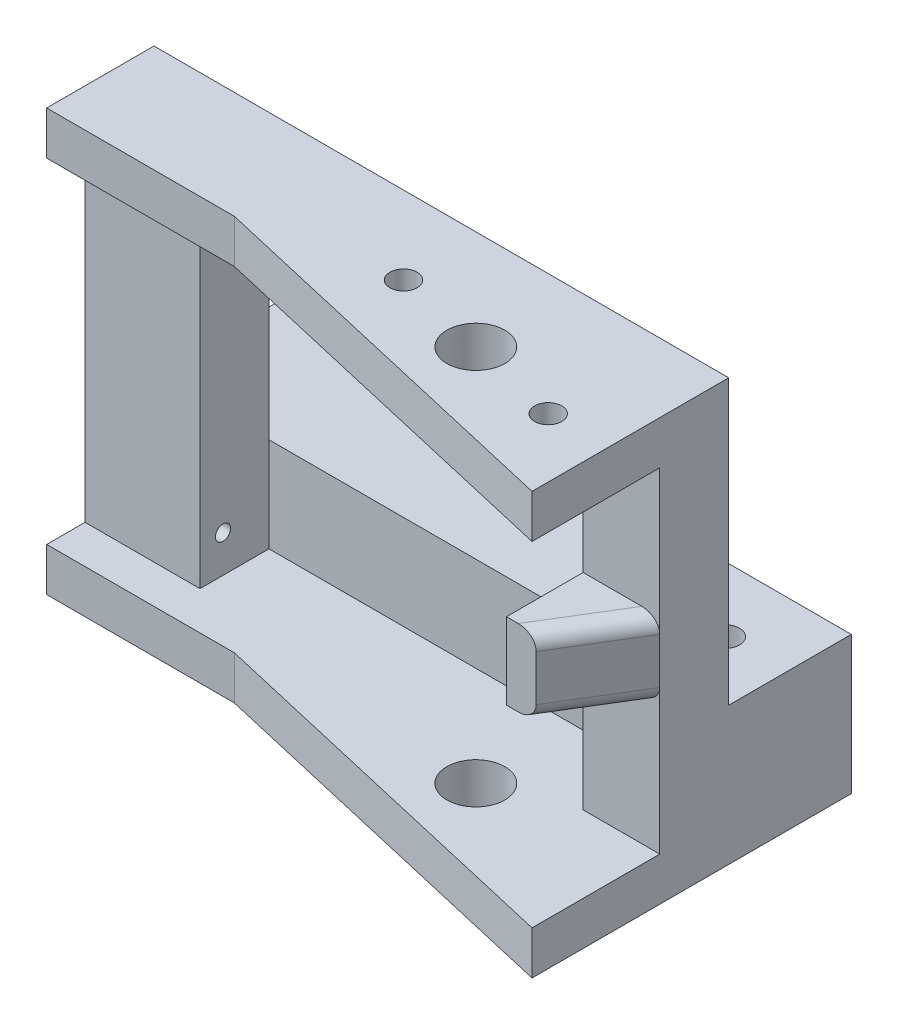
SolidWorks part; units mm, degrees
ref_plane "Front Plane" through (0, 0, 0) normal (0, 0, 1) x (1, 0, 0)
ref_plane "Top Plane" through (0, 0, 0) normal (0, 1, 0) x (1, 0, 0)
ref_plane "Right Plane" through (0, 0, 0) normal (1, 0, 0) x (0, 0, -1)
sketch "Sketch1" plane through (0, 0, 0) normal (0, 0, 1) x (1, 0, 0)
  line L1 (57.15, -34.925) -> (-57.15, -34.925)
  line L2 (57.15, -34.925) -> (57.15, 34.925)
  line L3 (57.15, 34.925) -> (-57.15, 34.925)
  line L4 (-57.15, -34.925) -> (-57.15, 34.925)
  line L5 (57.15, -34.925) -> (-57.15, 34.925) construction
  line L6 (57.15, 34.925) -> (-57.15, -34.925) construction
  point P0 (0, 0)
  dimension "D1" = 69.85
  dimension "D2" = 114.3
extrude "Boss-Extrude1" add sketch "Sketch1" along normal blind 57.15
sketch "Sketch2" plane through (0, 0, 57.15) normal (0, 0, 1) x (1, 0, 0)
  line L0 (-57.15, 34.925) -> (-57.15, -34.925) construction
  line L1 (57.15, -27.725) -> (-57.15, -27.725)
  line L2 (57.15, -27.725) -> (57.15, 27.725)
  line L3 (57.15, 27.725) -> (-57.15, 27.725)
  line L4 (-57.15, -27.725) -> (-57.15, 27.725)
  line L5 (57.15, -27.725) -> (-57.15, 27.725) construction
  line L6 (57.15, 27.725) -> (-57.15, -27.725) construction
  line L7 (57.15, 34.925) -> (-57.15, 34.925) construction
  point P0 (0, 0)
  dimension "D1" = 7.2
extrude "Cut-Extrude2" cut sketch "Sketch2" against normal blind 25.4
sketch "Sketch3" plane through (0, 0, 0) normal (0, 0, -1) x (-1, 0, 0)
  line L0 (-57.15, -34.925) -> (-57.15, 34.925) construction
  line L1 (57.15, 34.925) -> (-57.15, 34.925)
  line L2 (57.15, 34.925) -> (57.15, -12.065)
  line L3 (57.15, -12.065) -> (-57.15, -12.065)
  line L4 (-57.15, 34.925) -> (-57.15, -12.065)
  dimension "D1" = 46.99
extrude "Cut-Extrude3" cut sketch "Sketch3" against normal blind 20.32
sketch "Sketch5" plane through (0, -34.925, 0) normal (0, -1, 0) x (1, 0, 0)
  line L0 (-3.81, 10.79) -> (46.99, 10.79) construction
  line L1 (57.15, 20.32) -> (-57.15, 20.32) construction
  line L2 (57.15, 57.15) -> (57.15, 0) construction
  circle A0 centre (-3.81, 10.79) radius 2.415
  circle A1 centre (46.99, 10.79) radius 2.415
  dimension "D3" = 4.83
  dimension "D4" = 10.16
  dimension "D1" = 9.53
  dimension "D2" = 50.8
extrude "Cut-Extrude4" cut sketch "Sketch5" against normal blind 25.4
sketch "Sketch6" plane through (0, 0, 20.32) normal (0, 0, -1) x (-1, 0, 0)
  line L0 (-49.405, -12.065) -> (6.225, -12.065) construction
  line L1 (-49.405, -12.065) -> (-49.405, -34.925) construction
  line L2 (6.225, -34.925) -> (6.225, -12.065) construction
  line L3 (-57.15, -12.065) -> (57.15, -12.065) construction
  circle A1 centre (-5.08, -1.524) radius 2.2225
  dimension "D3" = 4.445
extrude "Cut-Extrude5" cut sketch "Sketch6" against normal blind 5.08
sketch "Sketch7" plane through (0, -34.925, 0) normal (0, -1, 0) x (1, 0, 0)
  line L0 (57.15, 57.15) -> (57.15, 0) construction
  line L2 (-57.15, 31.75) -> (57.15, 31.75) construction
  circle A0 centre (31.75, 36.83) radius 4.8
  dimension "D1" = 9.6
  dimension "D2" = 25.4
  dimension "D3" = 5.08
extrude "Cut-Extrude6" cut sketch "Sketch7" against normal up to surface (69.85 mm away) up to face at (0, 34.925, 38.735)
sketch "Sketch8" plane through (0, 34.925, 0) normal (0, 1, 0) x (1, 0, 0)
  line L0 (16.1601, -33.2308) -> (47.3399, -40.4292) construction
  line L1 (57.15, -31.75) -> (-57.15, -31.75) construction
  circle A0 centre (31.75, -36.83) radius 16 construction
  circle A1 centre (16.1601, -33.2308) radius 2.25
  circle A2 centre (47.3399, -40.4292) radius 2.25
  dimension "D1" = 32
  dimension "D2" = 4.5
  dimension "D3" = 13
sketch "Sketch9" plane through (0, 0, 31.75) normal (0, 0, 1) x (1, 0, 0)
  line L0 (57.15, 34.925) -> (-57.15, 34.925) construction
  line L5 (57.15, 27.725) -> (-57.15, 27.725) construction
  line L6 (-19.05, 27.725) -> (44.45, 27.725)
  line L7 (-19.05, 27.725) -> (-19.05, -27.725)
  line L8 (-19.05, -27.725) -> (44.45, -27.725)
  line L9 (44.45, 27.725) -> (44.45, -27.725)
  line L10 (-57.15, -27.725) -> (57.15, -27.725) construction
  line L11 (-57.15, 27.725) -> (-57.15, -27.725) construction
  line L12 (57.15, -27.725) -> (57.15, 27.725) construction
  line L13 (-57.15, -34.925) -> (-38.1, -34.925)
  line L14 (-57.15, -34.925) -> (-57.15, 34.925)
  line L15 (-57.15, 34.925) -> (-38.1, 34.925)
  line L16 (-38.1, -34.925) -> (-38.1, 34.925)
  line L17 (-57.15, -34.925) -> (-38.1, 34.925) construction
  line L18 (-57.15, 34.925) -> (-38.1, -34.925) construction
  line L19 (-57.15, -34.925) -> (57.15, -34.925) construction
  point P5 (-47.625, 0)
  dimension "D1" = 12.7
  dimension "25in" = 38.1
  dimension "D2" = 19.05
extrude "Cut-Extrude7" cut sketch "Sketch9" against normal through all both and the other way through all
extrude "Cut-Extrude8" cut sketch "Sketch8" against normal up to next
sketch "Sketch10" [suppressed] plane through (0, 0, 29.21) normal (0, 0, 1) x (1, 0, 0)
  line L1 (-30.607, -1.778) -> (-30.607, -6.604) construction
  circle A0 centre (-33.2489, -4.191) radius 2.286
  point P5 (-30.607, -4.191)
  dimension "D1" = 4.572
sketch "Sketch11" [suppressed] plane through (0, 0, 21.59) normal (0, 0, -1) x (-1, 0, 0)
  circle A0 centre (33.2489, -4.191) radius 2.286
  dimension "D1" = 4.572
extrude "Cut-Extrude9" [suppressed] cut sketch "Sketch11" against normal blind 3.81
sketch "Sketch12" plane through (-19.05, 0, 0) normal (1, 0, 0) x (0, 0, -1)
  line L0 (-31.75, -27.725) -> (-31.75, 27.725) construction
  line L1 (-27.94, -21.59) -> (-27.94, 21.59) construction
  line L2 (-20.32, 27.725) -> (-20.32, -12.065) construction
  circle A0 centre (-27.94, -21.59) radius 1.25
  circle A1 centre (-27.94, 21.59) radius 1.25
  point P0 (-31.75, 0)
  point P8 (-27.94, 0)
  dimension "D1" = 2.5
  dimension "D2" = 7.62
  dimension "D3" = 43.18
extrude "Cut-Extrude10" cut sketch "Sketch12" against normal up to surface (19.05 mm away) up to face at (-38.1, -2.413, 33.274)
sketch "Sketch13" plane through (0, 34.925, 0) normal (0, 1, 0) x (1, 0, 0)
  line L0 (-38.1, -38.1077) -> (-6.9983, -38.1077)
  line L1 (-6.9983, -38.1077) -> (75.4829, -57.15)
  line L2 (57.15, -57.15) -> (-38.1, -57.15) construction
  line L3 (47.3399, -40.4292) -> (16.1601, -33.2308) construction
  line L4 (-38.1, -38.1077) -> (-38.1, -57.15)
  line L5 (-38.1, -57.15) -> (75.4829, -57.15)
  line L6 (-38.1, -20.32) -> (-38.1, -57.15) construction
extrude "Cut-Extrude12" cut sketch "Sketch13" against normal through all
sketch "Sketch14" plane through (44.45, 0, 0) normal (-1, 0, 0) x (0, 0, 1)
  line L0 (0, -27.725) -> (31.75, -27.725) construction
  line L1 (20.32, -12.065) -> (0, -12.065)
  line L2 (20.32, -12.065) -> (20.32, -27.725)
  line L3 (20.32, -27.725) -> (0, -27.725)
  line L4 (0, -12.065) -> (0, -27.725)
extrude "Boss-Extrude2" add sketch "Sketch14" along normal up to next
sketch "Sketch16" plane through (0, 0, 31.75) normal (0, 0, 1) x (1, 0, 0)
  line L0 (44.45, -27.725) -> (44.45, 27.725) construction
  line L1 (57.15, -6.35) -> (44.45, -6.35)
  line L2 (57.15, -6.35) -> (57.15, 6.35)
  line L3 (57.15, 6.35) -> (44.45, 6.35)
  line L4 (44.45, -6.35) -> (44.45, 6.35)
  line L5 (57.15, -6.35) -> (44.45, 6.35) construction
  line L6 (57.15, 6.35) -> (44.45, -6.35) construction
  line L7 (57.15, 6.35) -> (57.15, -6.35) construction
  line L9 (57.15, -27.725) -> (57.15, 27.725) construction
  point P0 (50.8, 0)
  point P7 (57.15, 0)
  dimension "D1" = 12.7
extrude "Boss-Extrude3" add sketch "Sketch16" along normal blind 12.7
sketch "Sketch17" plane through (0, 6.35, 0) normal (0, 1, 0) x (1, 0, 0)
  line L0 (49.375, -44.45) -> (57.15, -31.75)
  line L1 (57.15, -44.45) -> (57.15, -31.75) construction
  line L2 (57.15, -31.75) -> (44.45, -31.75) construction
  line L3 (57.15, -31.75) -> (57.15, -44.45)
  line L4 (57.15, -44.45) -> (49.375, -44.45)
  line L5 (57.15, -44.45) -> (44.45, -44.45) construction
extrude "Cut-Extrude14" cut sketch "Sketch17" against normal blind 12.7
fillet "Fillet4" radius 2.54 2 edges at (53.2625, -6.35, 38.1) (53.2625, 6.35, 38.1)
